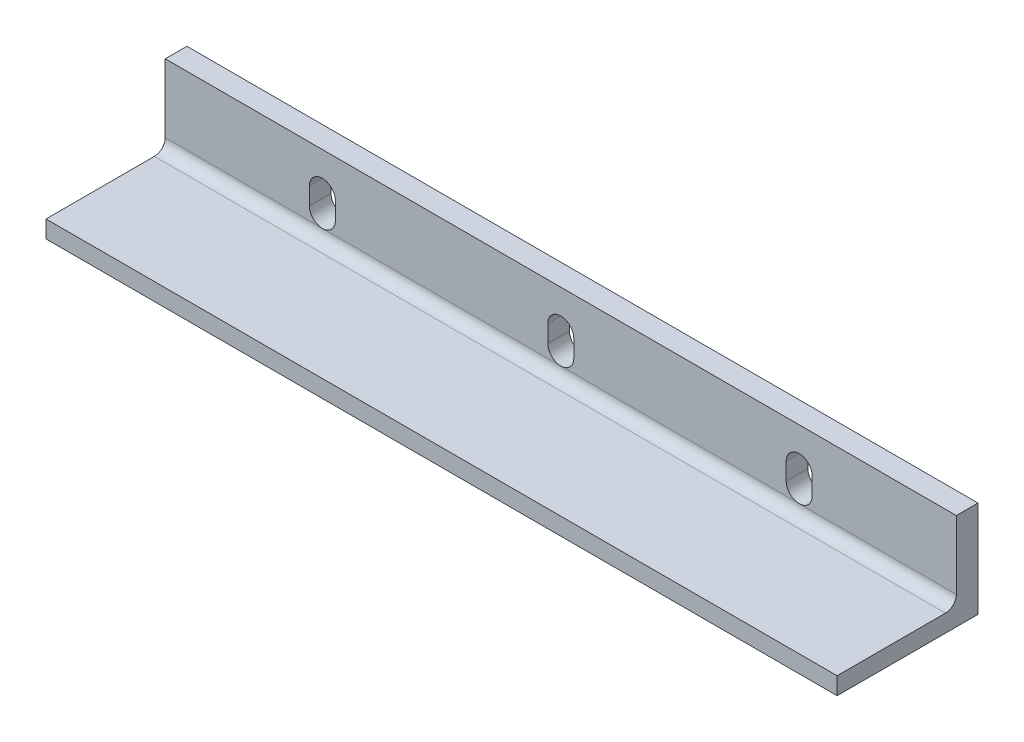
SolidWorks part; units mm, degrees
material "FR4_stuffedProtoboard"
ref_plane "Front Plane" through (0, 0, 0) normal (0, 0, 1) x (1, 0, 0)
ref_plane "Top Plane" through (0, 0, 0) normal (0, 1, 0) x (1, 0, 0)
ref_plane "Right Plane" through (0, 0, 0) normal (1, 0, 0) x (0, 0, -1)
sketch "Sketch1" plane through (0, 0, 0) normal (0, 1, 0) x (1, 0, 0)
  line L1 (-36.5, -6.5) -> (36.5, -6.5)
  line L2 (-36.5, -6.5) -> (-36.5, 6.5)
  line L3 (-36.5, 6.5) -> (36.5, 6.5)
  line L4 (36.5, -6.5) -> (36.5, 6.5)
  line L5 (-36.5, -6.5) -> (36.5, 6.5) construction
  line L6 (-36.5, 6.5) -> (36.5, -6.5) construction
  point P0 (0, 0)
  dimension "D1" = 13
  dimension "D2" = 73
extrude "Boss-Extrude1" add sketch "Sketch1" along normal blind 1.6
sketch "Sketch2" plane through (0, 1.6, 0) normal (0, 1, 0) x (1, 0, 0)
  line L0 (36.5, -6.5) -> (36.5, 6.5) construction
  line L1 (-36.5, 6.5) -> (36.5, 6.5)
  line L2 (-36.5, 6.5) -> (-36.5, 4.5)
  line L3 (-36.5, 4.5) -> (36.5, 4.5)
  line L4 (36.5, 6.5) -> (36.5, 4.5)
  dimension "D1" = 2
extrude "Boss-Extrude2" add sketch "Sketch2" along normal blind 7.3
fillet "Fillet1" radius 1 1 edges at (0, 1.6, -4.5)
sketch "Sketch3" plane through (0, 0, -6.5) normal (0, 0, 1) x (1, 0, 0)
  line L0 (0, 0) -> (0, 4.6) construction
  line L1 (22, 4.6) -> (-22, 4.6) construction
  point P6 (0, 4.6)
  dimension "D1" = 4.6
  dimension "D2" = 44
hole_wizard "M2 Clearance Slot1" positions "Sketch7" profile "Sketch8" size "M2" standard "ANSI Metric" slot yes end condition through all
sketch "Sketch7" plane through (0, 0, -4.5) normal (0, 0, 1) x (1, 0, 0)
  line L0 (-22, 2.6) -> (-22, 6.6) construction
  point P14 (-22, 4.6)
  point P19 (0, 4.6)
  point P22 (22, 4.6)
  dimension "D1" = 4
sketch "Sketch8" plane through (-22, 4.6, -4.5) normal (1, 0, 0) x (0, -1, 0)
  line L0 (0, 0) -> (0, 2)
  line L1 (0, 2) -> (1.2, 2)
  line L2 (1.2, 2) -> (1.2, 0)
  line L5 (1.2, 0) -> (0, 0)
  line L11 (0, -6.35) -> (0, 107.95) construction
  dimension "Thru Hole Dia." = 2.4
  dimension "Thru Hole Depth" = 2
